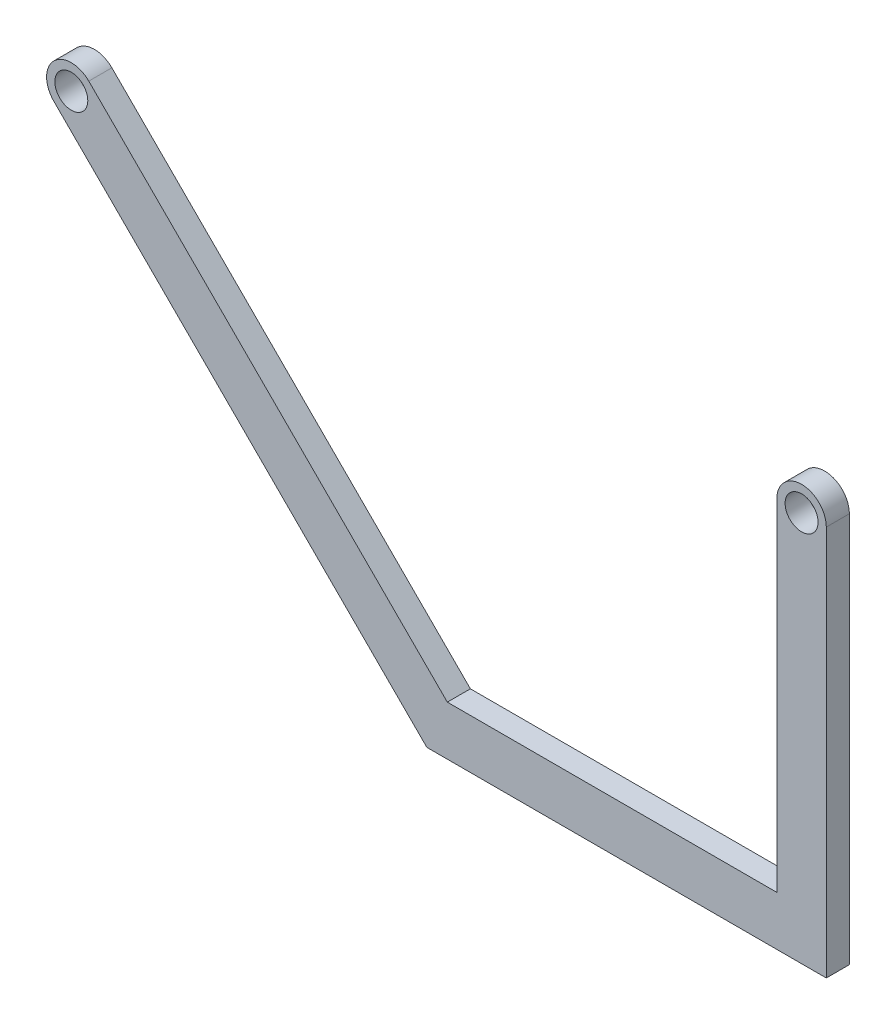
SolidWorks part; units mm, degrees
ref_plane "Front Plane" through (0, 0, 0) normal (0, 0, 1) x (1, 0, 0)
ref_plane "Top Plane" through (0, 0, 0) normal (0, 1, 0) x (1, 0, 0)
ref_plane "Right Plane" through (0, 0, 0) normal (1, 0, 0) x (0, 0, -1)
sketch "Sketch1" plane through (0, 0, 0) normal (0, 0, 1) x (1, 0, 0)
  line L0 (46.3363, 120.396) -> (46.3363, 15.24)
  line L1 (46.3363, 15.24) -> (-55.2637, 15.24)
  line L2 (-55.2637, 15.24) -> (-165.8078, 125.7842)
  line L3 (61.5763, 120.396) -> (61.5763, 0)
  line L4 (-176.5842, 115.0078) -> (-61.5763, 0)
  line L5 (-61.5763, 0) -> (61.5763, 0)
  line L6 (55, 0) -> (-55, 0) construction
  arc A0 (46.3363, 120.396) -> (61.5763, 120.396) centre (53.9563, 120.396) cw
  arc A1 (-165.8078, 125.7842) -> (-176.5842, 115.0078) centre (-171.196, 120.396) ccw
  point P12 (0, 0)
  dimension "D1" = 15.24
  dimension "D2" = 15.24
  dimension "D3" = 15.24
  dimension "D4" = 105.156
  dimension "D5" = 101.6
  dimension "D6" = 135
extrude "Boss-Extrude1" add sketch "Sketch1" along normal blind 3.556 and the other way blind 3.556
hole_wizard "3/4 (0.4) Diameter Hole1" positions "Sketch2" profile "Sketch3" hole size "3/4" standard "ANSI Inch" end condition through all
sketch "Sketch2" plane through (0, 0, 3.556) normal (0, 0, 1) x (1, 0, 0)
  point P0 (-171.196, 120.396)
  point P3 (53.9563, 120.396)
sketch "Sketch3" plane through (-171.196, 120.396, 3.556) normal (1, 0, 0) x (0, -1, 0)
  line L0 (0, 0) -> (0, 7.112)
  line L1 (0, 7.112) -> (5.08, 7.112)
  line L2 (5.08, 7.112) -> (5.08, 0)
  line L5 (5.08, 0) -> (0, 0)
  line L11 (0, -6.35) -> (0, 107.95) construction
  dimension "Thru Hole Dia." = 10.16
  dimension "Thru Hole Depth" = 7.112
